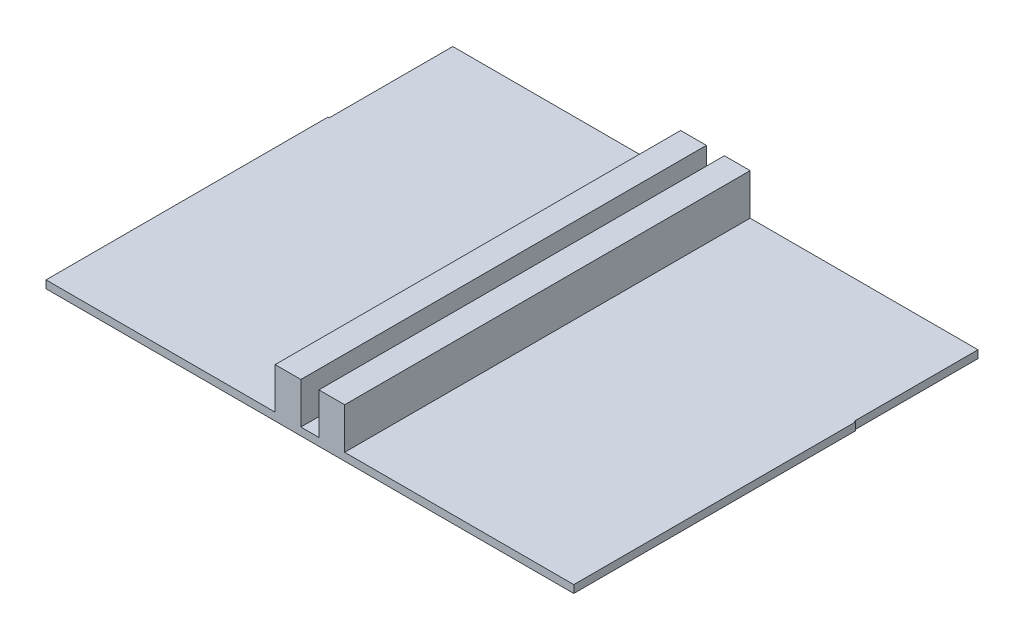
SolidWorks part; units mm, degrees
ref_plane "Front Plane" through (0, 0, 0) normal (0, 0, 1) x (1, 0, 0)
ref_plane "Top Plane" through (0, 0, 0) normal (0, 1, 0) x (1, 0, 0)
ref_plane "Right Plane" through (0, 0, 0) normal (1, 0, 0) x (0, 0, -1)
sketch "Sketch1" plane through (0, 0, 0) normal (0, 1, 0) x (1, 0, 0)
  line L0 (0, 15.8) -> (0, -15.8) construction
  line L1 (-10.55, -15.8) -> (10.55, -15.8)
  line L2 (-10.55, -15.8) -> (-10.55, 15.8)
  line L3 (-10.55, 15.8) -> (10.55, 15.8)
  line L4 (10.55, -15.8) -> (10.55, 15.8)
  line L5 (-10.55, -15.8) -> (10.55, 15.8) construction
  line L6 (-10.55, 15.8) -> (10.55, -15.8) construction
  line L7 (-10.25, 15.8) -> (-10.25, -15.8)
  line L8 (10.25, 15.8) -> (10.25, -15.8)
  line L9 (-10.55, 11) -> (10.55, 11)
  line L10 (-0.3, 15.8) -> (-0.3, 11)
  line L11 (0.3, 15.8) -> (0.3, 11)
  line L12 (-10.55, 0) -> (10.55, 0)
  line L13 (-10.5, -15.75) -> (-10.5, 15.75)
  line L14 (-10.5, 15.75) -> (10.5, 15.75)
  line L15 (10.5, -15.75) -> (10.5, 15.75)
  line L16 (-10.5, -15.75) -> (10.5, -15.75)
  line L17 (-0.35, 15.8) -> (-0.35, 11)
  line L18 (-10.55, 10.95) -> (10.55, 10.95)
  line L19 (0.35, 15.8) -> (0.35, 11)
  line L20 (-0.35, 11) -> (-0.35, 10.95)
  line L21 (0.35, 11) -> (0.35, 10.95)
  line L22 (-10.2, 15.8) -> (-10.2, -15.8)
  line L23 (10.2, 15.8) -> (10.2, -15.8)
  point P0 (0, 0)
  point P9 (-10.25, 15.8)
  point P14 (-10.55, 11)
  point P17 (-0.3, 15.8)
  point P39 (0, 0)
  point P40 (0, 0)
  point P41 (0, 0)
  point P42 (0, 0)
  point P43 (0, 0)
  point P44 (0, 0)
  dimension "D1" = 0.05
  dimension "D2" = 0.05
  dimension "D3" = 0.05
  dimension "D4" = 0.05
extrude "Boss-Extrude1" add sketch "Sketch1" along normal blind 0.3 contours L14 L22 L9 L17 | L23 L14 L19 L9 | L9 L22 L18 L20 | L23 L9 L21 L18 | L21 L9 L20 L18 | L23 L18 L22 L12 | L22 L18 L7 L12 | L18 L13 L12 L7 | L18 L8 L12 L15 | L18 L23 L12 L8 region at (-10.375, 0, -5.475) region at (-10.225, 0, -5.475) region at (0, 0, -5.475) region at (10.225, 0, -5.475) region at (-5.275, 0, -10.975) region at (10.375, 0, -5.475) region at (5.275, 0, -10.975) region at (0, 0, -10.975) region at (-5.275, 0, -13.375) region at (5.275, 0, -13.375)
sketch "Sketch2" plane through (0, 0.3, 0) normal (0, 1, 0) x (1, 0, 0)
  line L0 (-10.5, 0) -> (10.5, 0) construction
  line L1 (-0.35, 15.75) -> (-1.35, 15.75)
  line L2 (-0.35, 15.75) -> (-0.35, 0)
  line L3 (-0.35, 0) -> (-1.35, 0)
  line L4 (-1.35, 15.75) -> (-1.35, 0)
  line L5 (0, 11) -> (0, 0) construction
  line L6 (-0.35, 11) -> (0.35, 11) construction
  line L7 (0.35, 0) -> (1.35, 0)
  line L8 (1.35, 15.75) -> (1.35, 0)
  line L9 (0.35, 15.75) -> (1.35, 15.75)
  line L10 (0.35, 15.75) -> (0.35, 0)
extrude "Boss-Extrude2" add sketch "Sketch2" along normal blind 1.6
extrude "Cut-Extrude2" cut sketch "Sketch1<3>" along normal blind 10 contours L18 L13 L12 L7 | L18 L8 L12 L15 region at (-10.375, 0, -5.475) region at (10.375, 0, -5.475)
sketch "Sketch1<3>" plane through (0, 0, 0) normal (0, 1, 0) x (1, 0, 0) same geometry as "Sketch1"
